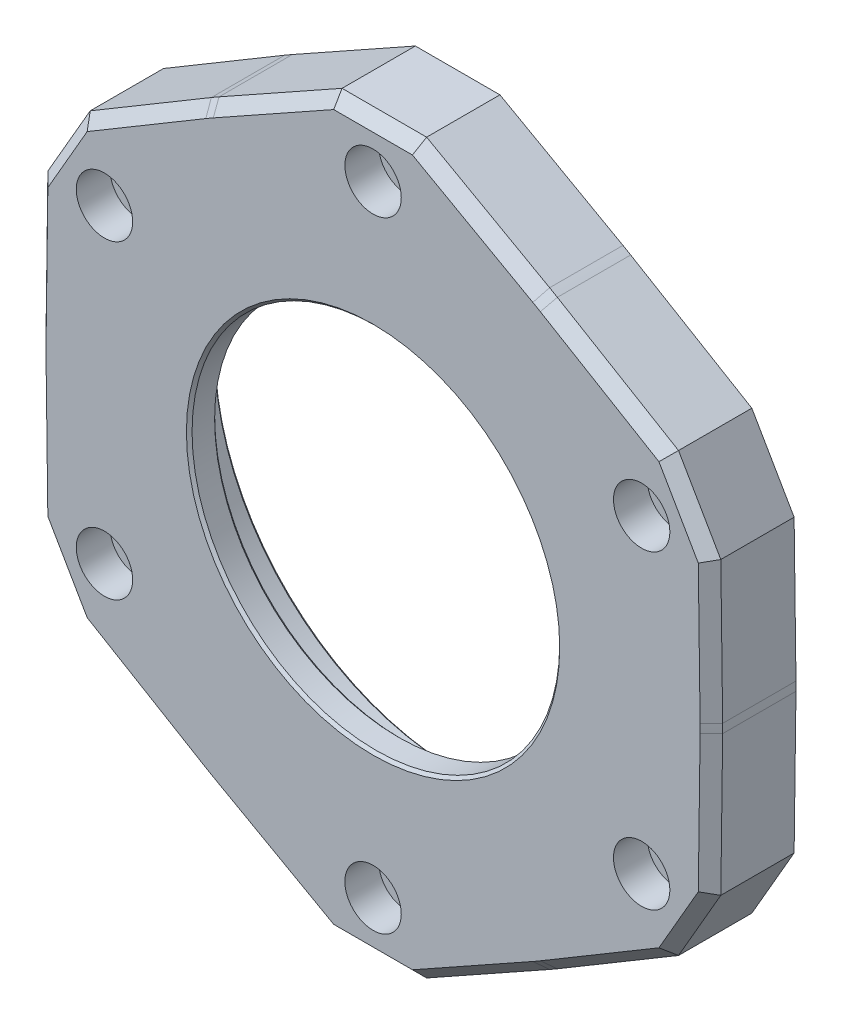
SolidWorks part; units mm, degrees
ref_plane "Front Plane" through (0, 0, 0) normal (0, 0, 1) x (1, 0, 0)
ref_plane "Top Plane" through (0, 0, 0) normal (0, 1, 0) x (1, 0, 0)
ref_plane "Right Plane" through (0, 0, 0) normal (1, 0, 0) x (0, 0, -1)
sketch "Sketch1" plane through (0, 0, 0) normal (0, 0, 1) x (1, 0, 0)
  circle A0 centre (0, 0) radius 60
  circle A1 centre (0, 0) radius 55 construction
  circle A2 centre (0, 55) radius 2.55
  circle A3 centre (47.6314, 27.5) radius 2.55
  circle A4 centre (47.6314, -27.5) radius 2.55
  circle A5 centre (0, -55) radius 2.55
  circle A6 centre (-47.6314, -27.5) radius 2.55
  circle A7 centre (-47.6314, 27.5) radius 2.55
  circle A8 centre (0, 0) radius 42.55
  point P18 (0, 0)
  dimension "D1" = 120
  dimension "D2" = 110
  dimension "D3" = 5.1
  dimension "D5" = 85.1
  dimension "D4" = 6
extrude "Boss-Extrude1" add sketch "Sketch1" along normal blind 15
sketch "Sketch3" plane through (0, 0, 15) normal (0, 0, 1) x (1, 0, 0)
  circle A0 centre (0, 0) radius 42.55
  circle A1 centre (0, 0) radius 32.6
  dimension "D1" = 85.1
  dimension "D2" = 65.2
extrude "Boss-Extrude2" add sketch "Sketch3" against normal blind 5
sketch "Sketch7" plane through (0, 0, 0) normal (0, 0, -1) x (-1, 0, 0)
  line L0 (-29.3133, 52.352) -> (-7.5, 64.5659)
  line L1 (-7.5, 64.5659) -> (7.5, 64.5659)
  line L2 (7.5, 64.5659) -> (29.3133, 52.352)
  line L3 (59.6657, 25.7877) -> (59.9948, 0.7899)
  line L4 (52.1657, 38.7781) -> (59.6657, 25.7877)
  line L5 (30.6815, 51.5621) -> (52.1657, 38.7781)
  line L6 (52.1657, -38.7781) -> (30.6815, -51.5621)
  line L7 (59.6657, -25.7877) -> (52.1657, -38.7781)
  line L8 (59.9948, -0.7899) -> (59.6657, -25.7877)
  line L9 (-7.5, -64.5659) -> (-29.3133, -52.352)
  line L10 (7.5, -64.5659) -> (-7.5, -64.5659)
  line L11 (29.3133, -52.352) -> (7.5, -64.5659)
  line L12 (-59.6657, -25.7877) -> (-59.9948, -0.7899)
  line L13 (-52.1657, -38.7781) -> (-59.6657, -25.7877)
  line L14 (-30.6815, -51.5621) -> (-52.1657, -38.7781)
  line L15 (-52.1657, 38.7781) -> (-30.6815, 51.5621)
  line L16 (-59.6657, 25.7877) -> (-52.1657, 38.7781)
  line L17 (-59.9948, 0.7899) -> (-59.6657, 25.7877)
  circle A0 centre (0, 0) radius 65 construction
  circle A1 centre (0, 0) radius 60 construction
  arc A2 (-30.6815, 51.5621) -> (-59.9948, 0.7899) centre (0, 0) ccw
  arc A3 (29.3133, 52.352) -> (-29.3133, 52.352) centre (0, 0) ccw
  arc A4 (59.9948, 0.7899) -> (30.6815, 51.5621) centre (0, 0) ccw
  arc A5 (30.6815, -51.5621) -> (59.9948, -0.7899) centre (0, 0) ccw
  arc A6 (-29.3133, -52.352) -> (29.3133, -52.352) centre (0, 0) ccw
  arc A7 (-59.9948, -0.7899) -> (-30.6815, -51.5621) centre (0, 0) ccw
  point P8 (0, 64.5659)
  point P35 (0, 0)
  dimension "D1" = 130
  dimension "D2" = 15
  dimension "D3" = 6
extrude "Boss-Extrude3" add sketch "Sketch7" against normal up to surface (15 mm away) up to face at (-45.0814, -27.5, 15)
sketch "Sketch8" plane through (0, 0, 15) normal (0, 0, 1) x (1, 0, 0)
  circle A0 centre (0, 55) radius 5
  circle A1 centre (47.6314, 27.5) radius 5
  circle A2 centre (47.6314, -27.5) radius 5
  circle A3 centre (0, -55) radius 5
  circle A4 centre (-47.6314, -27.5) radius 5
  circle A5 centre (-47.6314, 27.5) radius 5
  point P15 (0, 0)
  dimension "D1" = 10
  dimension "D2" = 6
extrude "Cut-Extrude1" cut sketch "Sketch8" against normal blind 6
chamfer "Chamfer2" distance 0.5 angle 45 3 edges at (42.55, 0, 0) (32.6, 0, 10) (32.6, 0, 15)
chamfer "Chamfer3" distance 2 angle 45 24 edges at (-18.4067, 58.4589, 15) (0, 64.5659, 15) (18.4067, 58.4589, 15) (30, 51.9615, 15) (41.4236, 45.1701, 15) (55.9157, 32.2829, 15) (59.8302, 13.2888, 15) (60, 0, 15) (59.8302, -13.2888, 15) (55.9157, -32.2829, 15) (41.4236, -45.1701, 15) (30, -51.9615, 15) (18.4067, -58.4589, 15) (0, -64.5659, 15) (-18.4067, -58.4589, 15) (-30, -51.9615, 15) (-41.4236, -45.1701, 15) (-55.9157, -32.2829, 15) (-59.8302, -13.2888, 15) (-60, 0, 15) (-59.8302, 13.2888, 15) (-55.9157, 32.2829, 15) (-41.4236, 45.1701, 15) (-30, 51.9615, 15)
sketch "Sketch9" plane through (0, 0, 0) normal (0, 0, -1) x (-1, 0, 0)
  line L0 (0, 48) -> (0, 0) construction
  line L1 (0, 0) -> (-8.3351, 47.2708) construction
  circle A55 centre (0, 0) radius 48 construction
  circle A56 centre (-8.3351, 47.2708) radius 4.075
  circle A57 centre (8.3351, 47.2708) radius 4.075
  circle A58 centre (24, 41.5692) radius 4.075
  circle A59 centre (36.7701, 30.8538) radius 4.075
  circle A60 centre (45.1052, 16.417) radius 4.075
  circle A61 centre (48, 0) radius 4.075
  circle A62 centre (45.1052, -16.417) radius 4.075
  circle A63 centre (36.7701, -30.8538) radius 4.075
  circle A64 centre (24, -41.5692) radius 4.075
  circle A65 centre (8.3351, -47.2708) radius 4.075
  circle A66 centre (-8.3351, -47.2708) radius 4.075
  circle A67 centre (-24, -41.5692) radius 4.075
  circle A68 centre (-36.7701, -30.8538) radius 4.075
  circle A69 centre (-45.1052, -16.417) radius 4.075
  circle A70 centre (-48, 0) radius 4.075
  circle A71 centre (-45.1052, 16.417) radius 4.075
  circle A72 centre (-36.7701, 30.8538) radius 4.075
  circle A73 centre (-24, 41.5692) radius 4.075
  point P42 (0, 0)
  point P61 (0, 0)
  point P96 (0, 0)
  dimension "D1" = 96
  dimension "D3" = 8.15
  dimension "D4" = 18
  dimension "D2" = 10
extrude "Cut-Extrude2" cut sketch "Sketch9" against normal blind 7
